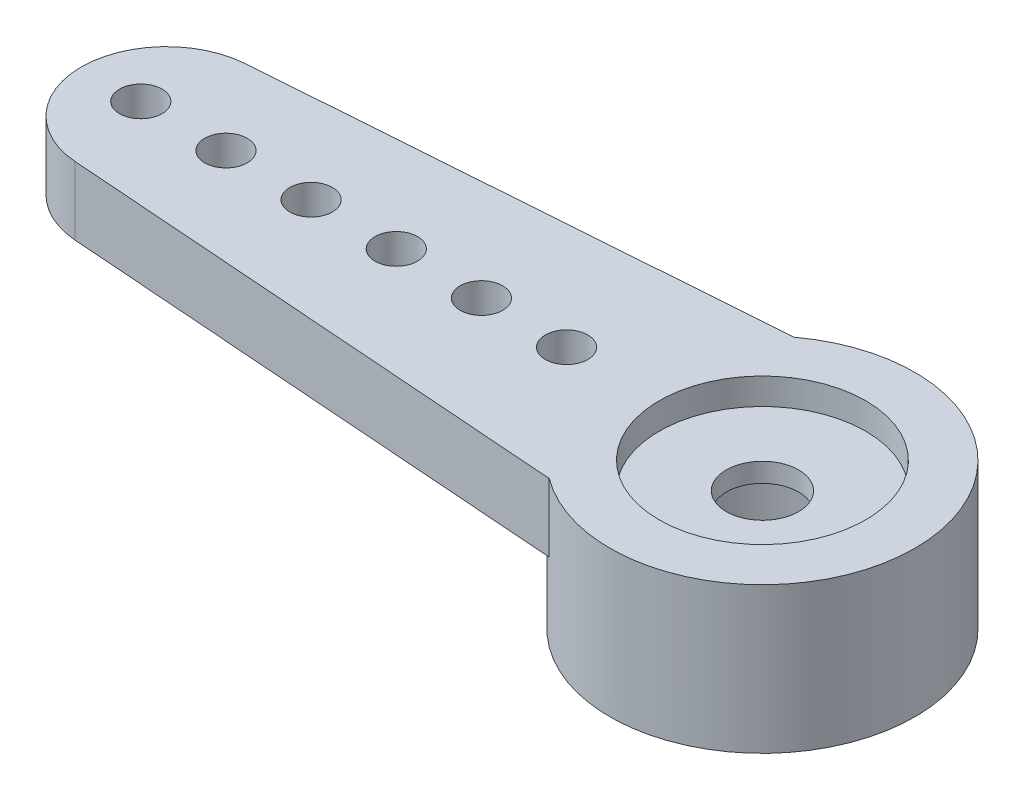
SolidWorks part; units mm, degrees
ref_plane "Alzado" through (0, 0, 0) normal (0, 0, 1) x (1, 0, 0)
ref_plane "Planta" through (0, 0, 0) normal (0, 1, 0) x (1, 0, 0)
ref_plane "Vista lateral" through (0, 0, 0) normal (1, 0, 0) x (0, 0, -1)
ref_plane "Plano1" through (0, 14.27, 0) normal (0, 1, 0) x (1, 0, 0)
sketch "Croquis1" plane through (0, 14.27, 0) normal (0, 1, 0) x (1, 0, 0)
  line L0 (8.0333, 3.025) -> (20.0462, 3.9053)
  line L1 (20.0462, 7.8947) -> (8.0333, 8.775)
  line L2 (3.7667, 8.775) -> (-8.2462, 7.8947)
  line L3 (-8.2462, 3.9053) -> (3.7667, 3.025)
  arc A0 (3.7667, 3.025) -> (8.0333, 3.025) centre (5.9, 5.9) ccw
  arc A1 (20.0462, 3.9053) -> (20.0462, 7.8947) centre (19.9, 5.9) ccw
  arc A2 (8.0333, 8.775) -> (3.7667, 8.775) centre (5.9, 5.9) ccw
  arc A3 (-8.2462, 7.8947) -> (-8.2462, 3.9053) centre (-8.1, 5.9) ccw
extrude "Saliente-Extruir1" add sketch "Croquis1" against normal blind 1.6
sketch "Croquis2" plane through (0, 12.67, 0) normal (0, -1, 0) x (1, 0, 0)
  circle A0 centre (5.9, -5.9) radius 3.58
extrude "Saliente-Extruir2" add sketch "Croquis2" along normal blind 1.83
ref_plane "Plano2" through (0, 0, -5.9) normal (0, 0, 1) x (1, 0, 0)
sketch "Croquis3" plane through (0, 0, -5.9) normal (0, 0, 1) x (1, 0, 0)
  line L0 (8.325, 14.27) -> (5.9, 14.27)
  line L1 (5.9, 14.27) -> (5.9, 10.84)
  line L2 (5.9, 10.84) -> (8.2, 10.84)
  line L3 (8.2, 10.84) -> (8.2, 13.2)
  line L4 (8.2, 13.2) -> (6.75, 13.2)
  line L5 (6.75, 13.2) -> (6.75, 13.65)
  line L6 (6.75, 13.65) -> (8.325, 13.65)
  line L7 (8.325, 13.65) -> (8.325, 14.27)
  line L8 (5.9, 14.27) -> (5.9, 10.84) construction
revolve "Cortar-Revolución1" cut sketch "Croquis3" angle 360 about L8 reverse direction yes
hole_wizard "Diámetro de taladro Ø1.0 (1)1" positions "Croquis5" profile "Croquis4" hole size "Ø1.0" standard "Ansi Metric"
sketch "Croquis5" plane through (0, 12.67, 0) normal (0, -1, 0) x (-1, 0, 0)
  point P0 (2.7, 5.9)
  point P1 (6.7, 5.9)
  point P2 (8.7, 5.9)
  point P3 (4.7, 5.9)
  point P4 (0.7, 5.9)
  point P5 (-10.5, 5.9)
  point P6 (-14.5, 5.9)
  point P7 (-18.5, 5.9)
  point P8 (-20.5, 5.9)
  point P9 (-16.5, 5.9)
  point P10 (-12.5, 5.9)
  point P11 (-1.3, 5.9)
sketch "Croquis4" plane through (-2.7, 12.67, -5.9) normal (1, 0, 0) x (0, 0, -1)
  line L0 (0, 0) -> (0, 1.6)
  line L1 (0, 1.6) -> (0.5, 1.6)
  line L2 (0.5, 1.6) -> (0.5, 0)
  line L5 (0.5, 0) -> (0, 0)
  line L11 (0, -6.35) -> (0, 107.95) construction
  dimension "Diámetro de taladro hasta el siguiente" = 1
  dimension "Profundidad de taladro hasta el siguiente" = 1.6
sketch "Croquis6" plane through (0, 10.84, 0) normal (0, -1, 0) x (1, 0, 0)
  line L0 (5.9, -9.48) -> (5.9, -13.2932)
  line L1 (5.9, -13.2932) -> (27.116, -13.2932)
  line L2 (27.116, -13.2932) -> (27.116, 2.205)
  line L3 (27.116, 2.205) -> (5.9, 2.205)
  line L4 (5.9, 2.205) -> (5.9, -2.32)
  arc A0 (5.9, -9.48) -> (5.9, -2.32) centre (5.9, -5.9) ccw
  circle A1 centre (5.9, -5.9) radius 3.58 construction
extrude "Cortar-Extruir1" cut sketch "Croquis6" against normal through all
